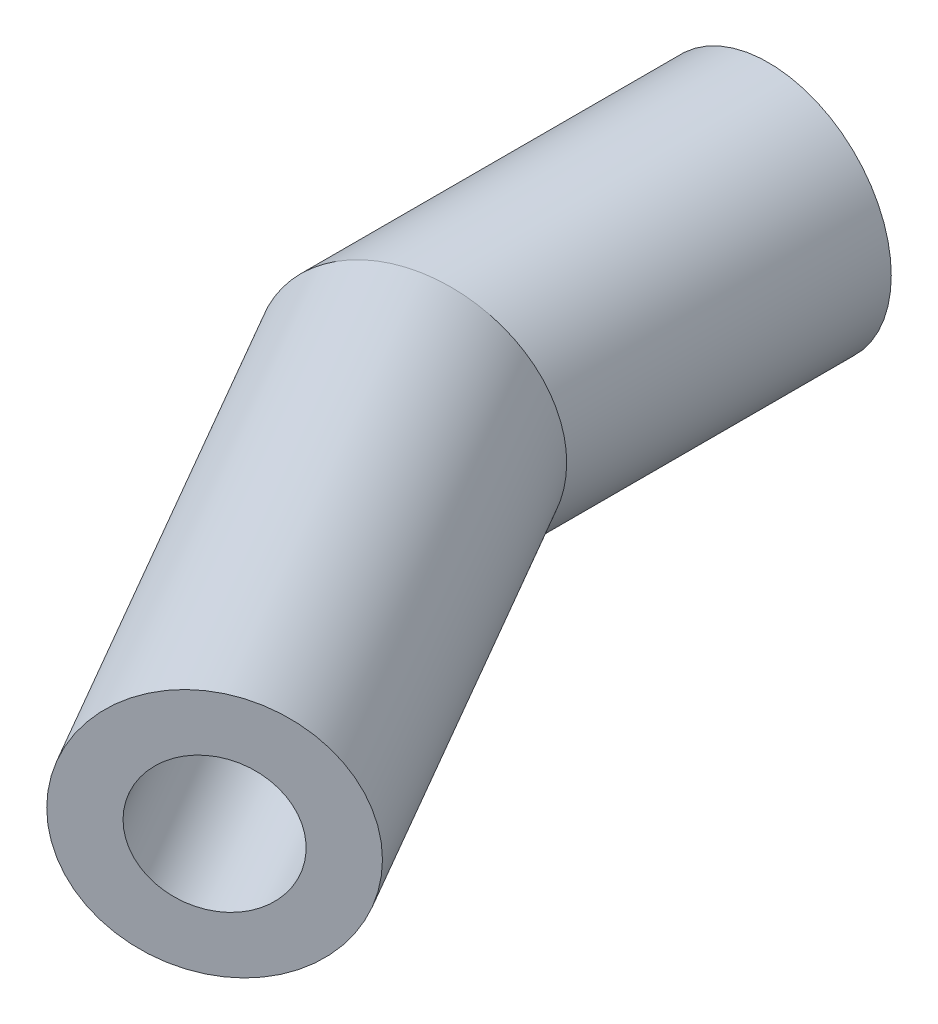
SolidWorks part; units mm, degrees
material "Silicon Rubber"
ref_plane "X-Y Datum" through (0, 0, 0) normal (0, 0, 1) x (1, 0, 0)
ref_plane "X-Z Datum" through (0, 0, 0) normal (0, 1, 0) x (1, 0, 0)
ref_plane "Y-Z Datum" through (0, 0, 0) normal (1, 0, 0) x (0, 0, -1)
sketch3d "3DSketch1"
  line L0 (0, 0, 0) -> (0, 0, 25.4)
  line L1 (0, 0, 25.4) -> (19.05, 0, 58.3956)
  line L2 (0, 0, 25.4) -> (20.0705, 0, 25.4) construction
  point P5 (0, 0, 0)
  dimension "D1" = 25.4
  dimension "D2" = 38.1
  dimension "D3" = 300
  dimension "D4" = 61.4243
sweep "Sweep1" add path "3DSketch1" circular profile diameter 17.4625 parameters "D3"=17.4625
sweep "Cut-Sweep1" cut path "3DSketch1<2>" circular profile diameter 9.525 parameters "D3"=9.525
sketch3d "3DSketch1<2>" same geometry as "3DSketch1"
sketch3d "3DSketch3"
  line L0 (0, 0, 0) -> (0, 0, 25.4) construction
  line L1 (0, 0, 25.4) -> (0, -4.7625, 25.4)
  line L2 (0, 0, 25.4) -> (-4.7625, 0, 25.4)
  circle A0 centre (0, 0, 25.4) radius 4.7625
  circle A1 centre (0, 0, 0) radius 4.7625 construction
  circle A2 centre (0, 0, 0) radius 4.7625 construction
  point P3 (0, 0, 20.6375)
  point P9 (0, 0, -4.7625)
  point P11 (0, 0, -4.7625)
  point P12 (0, 0, 0)
  dimension "D1" = 25.4
